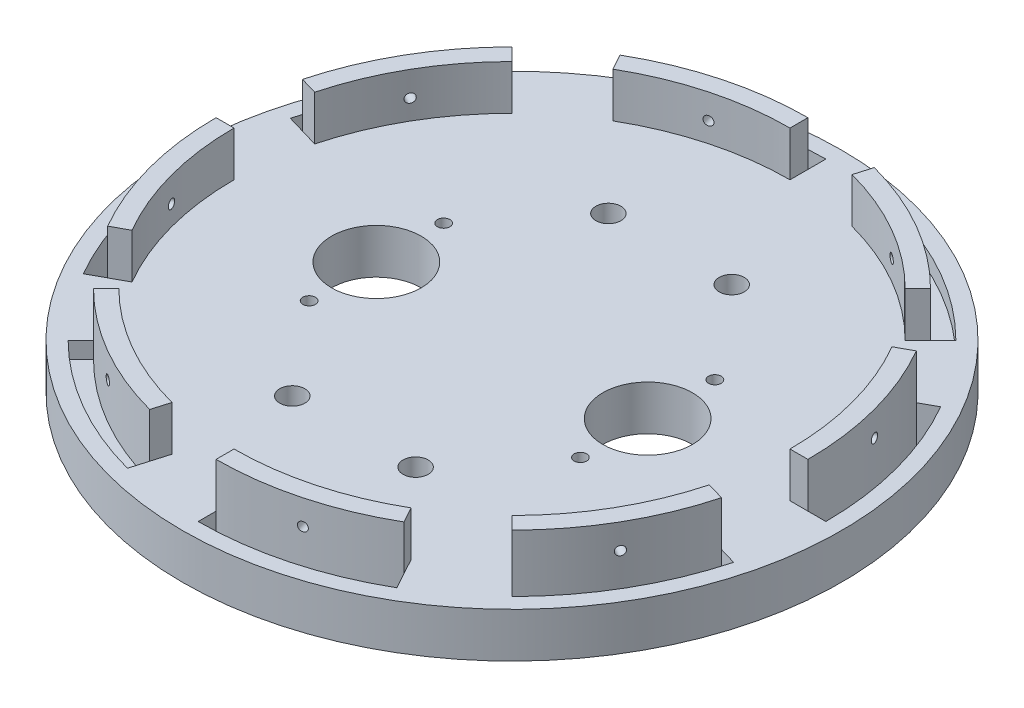
SolidWorks part; units mm, degrees
material "6061-T6 (SS)"
ref_plane "Front" through (0, 0, 0) normal (0, 0, 1) x (1, 0, 0)
ref_plane "Top" through (0, 0, 0) normal (0, 1, 0) x (1, 0, 0)
ref_plane "Right" through (0, 0, 0) normal (1, 0, 0) x (0, 0, -1)
sketch "Sketch1" plane through (0, 0, 0) normal (0, 1, 0) x (1, 0, 0)
  line L1 (0, 0) -> (127.635, 0)
  line L2 (0, 0) -> (0, 127.635)
  line L3 (0, 127.635) -> (127.635, 127.635)
  line L4 (127.635, 0) -> (127.635, 127.635)
  dimension "D1" = 127.635
  dimension "D2" = 127.635
extrude "Main Plate" add sketch "Sketch1" along normal blind 12.7
sketch "Sketch9" plane through (0, 12.7, 0) normal (0, 1, 0) x (1, 0, 0)
  circle A0 centre (63.8175, 63.8175) radius 93.345
  point P3 (0, 0)
  point P4 (0, 0)
  point P5 (0, 0)
  point P6 (0, 0)
  dimension "D1" = 186.69
  dimension "D2" = 63.8175
  dimension "D3" = 63.8175
extrude "Boss-Extrude1" add sketch "Sketch9" against normal up to surface (12.7 mm away) contours A0 up to face at (63.8175, 0, -63.8175)
sketch "Sketch11" plane through (0, 12.7, 0) normal (0, 1, 0) x (1, 0, 0)
  circle A0 centre (63.8175, 63.8175) radius 38.4175 construction
  circle A1 centre (63.8175, 63.8175) radius 42.8813 construction
  circle A2 centre (63.8175, 63.8175) radius 48.0528 construction
  point P3 (0, 0)
  point P5 (56.2292, 90.5407)
  point P8 (0, 0)
  dimension "D1" = 76.835
  dimension "D2" = 85.7626
  dimension "D3" = 96.1055
sketch "Sketch12" plane through (0, 12.7, 0) normal (0, 1, 0) x (1, 0, 0)
  line L0 (63.8175, 156.3529) -> (63.8175, -30.2474) construction
  line L1 (160.3603, 63.8175) -> (-31.9911, 63.8175) construction
sketch "Sketch2" plane through (0, 12.7, 0) normal (0, 1, 0) x (1, 0, 0)
  circle A0 centre (46.355, 108.585) radius 3.556
  circle A3 centre (63.8175, 63.8175) radius 48.0528 construction
  dimension "D1" = 7.112
extrude "U-Bolt Hole" cut sketch "Sketch2" against normal blind 12.7
pattern_linear "U-Bolt Pattern" count 2 spacing 34.925 along (1, 0, 0) count 2 spacing 89.535 along (0, 0, 1) of "U-Bolt Hole"
sketch "Sketch3" plane through (0, 12.7, 0) normal (0, 1, 0) x (1, 0, 0)
  circle A0 centre (25.4, 44.7675) radius 1.778
  circle A1 centre (63.8175, 63.8175) radius 42.8813 construction
  dimension "D1" = 3.556
extrude "Raptor Bolt Hole" cut sketch "Sketch3" against normal blind 12.7
pattern_linear "Raptor Bolt Pattern" count 2 spacing 38.1 along (0, 0, -1) count 2 spacing 76.835 along (1, 0, 0) of "Raptor Bolt Hole"
sketch "Sketch4" plane through (0, 12.7, 0) normal (0, 1, 0) x (1, 0, 0)
  circle A0 centre (25.4, 63.8175) radius 12.7
  circle A1 centre (63.8175, 63.8175) radius 38.4175 construction
  dimension "D1" = 25.4
extrude "Co2 Cylinder Hole" cut sketch "Sketch4" against normal blind 12.7
pattern_linear "Co2 Pattern" count 2 spacing 76.835 along (1, 0, 0) of "Co2 Cylinder Hole"
sketch "Sketch13" plane through (0, 12.7, 0) normal (0, 1, 0) x (1, 0, 0)
  line L0 (63.8175, 63.8175) -> (63.8175, 157.1625) construction
  line L1 (-50, 0) -> (50, 0) construction
  line L2 (63.8175, 147.6375) -> (63.8175, 152.7175)
  line L3 (19.4246, 140.8401) -> (21.8608, 136.3808)
  arc A0 (19.4246, 140.8401) -> (63.8175, 152.7175) centre (63.8175, 63.8175) cw
  arc A1 (21.8608, 136.3808) -> (63.8175, 147.6375) centre (63.8175, 63.8175) cw
  circle A2 centre (63.8175, 63.8175) radius 93.345 construction
  dimension "D1" = 83.82
  dimension "D2" = 88.9
  dimension "D3" = 43.942
  dimension "D4" = 46.482
extrude "Bottom support hole" cut sketch "Sketch13" against normal through all
sketch "Sketch14" plane through (0, 12.7, 0) normal (0, 1, 0) x (1, 0, 0)
  line L0 (63.8175, 147.6375) -> (63.8175, 142.5575)
  line L1 (24.297, 131.9213) -> (21.8608, 136.3808)
  line L4 (19.4246, 140.8401) -> (21.8608, 136.3808) construction
  arc A0 (63.8175, 142.5575) -> (24.297, 131.9213) centre (63.8175, 63.8175) ccw
  arc A1 (21.8608, 136.3808) -> (63.8175, 147.6375) centre (63.8175, 63.8175) cw
  point P6 (0, 0)
  point P9 (0, 0)
  dimension "D1" = 43.942
  dimension "D2" = 78.74
extrude "Bottom support guide" add sketch "Sketch14" along normal blind 12.7
ref_plane "Bottom bolt hole reference plane" through (-32.6653, 0, -121.7517) normal (0.2591, 0, 0.9658) x (0.9658, 0, -0.2591)
sketch "Sketch15" plane through (-32.6653, 0, -121.7517) normal (0.2591, 0, 0.9658) x (0.9658, 0, -0.2591)
  line L0 (99.8949, 25.4) -> (56.4544, 25.4) construction
  circle A0 centre (78.1779, 18.3381) radius 1.27
  dimension "D3" = 2.54
  dimension "D1" = 7.0619
  dimension "D2" = 21.717
extrude "Bottom bolt hole" cut sketch "Sketch15" against normal blind 12.7 and the other way blind 12.7
sketch "Sketch17" plane through (-29.8353, 12.7, 11.3946) normal (0, 1, 0) x (1, 0, 0)
  line L0 (93.6528, 75.2121) -> (27.6479, 141.217) construction
  line L2 (34.3831, 134.4818) -> (30.791, 138.0739)
  line L3 (7.7991, 98.2848) -> (12.675, 96.8542)
  line L4 (93.6528, 75.2121) -> (93.6528, 168.5571) construction
  arc A0 (7.7991, 98.2848) -> (30.791, 138.0739) centre (93.6528, 75.2121) cw
  arc A1 (12.675, 96.8542) -> (34.3831, 134.4818) centre (93.6528, 75.2121) cw
  circle A2 centre (93.6528, 75.2121) radius 93.345 construction
  point P3 (0, 0)
  point P6 (54.5809, 46.0878)
  point P8 (76.4675, 59.1533)
  point P9 (50.3325, 46.8384)
  point P13 (74.2776, 161.9751)
  point P14 (0, 0)
  point P15 (0, 0)
  point P18 (0, 0)
  dimension "D1" = 83.82
  dimension "D2" = 88.9
  dimension "D3" = 43.942
  dimension "D4" = 46.482
  dimension "D5" = 45
extrude "Top support hole" cut sketch "Sketch17" against normal blind 4.7625
sketch "Sketch19" plane through (-29.8353, 12.7, 11.3946) normal (0, 1, 0) x (1, 0, 0)
  line L0 (34.3831, 134.4818) -> (37.9752, 130.8897)
  line L1 (17.551, 95.4236) -> (12.675, 96.8542)
  line L2 (93.6528, 75.2121) -> (27.6479, 141.217) construction
  line L3 (7.7991, 98.2848) -> (12.675, 96.8542) construction
  arc A0 (37.9752, 130.8897) -> (17.551, 95.4236) centre (93.6528, 75.2121) ccw
  arc A1 (12.675, 96.8542) -> (34.3831, 134.4818) centre (93.6528, 75.2121) cw
  point P3 (0, 0)
  point P6 (0, 0)
  point P7 (0, 0)
  point P8 (-2.2794, 102.3671)
  point P9 (0, 0)
  point P10 (0, 0)
  point P11 (-2.9908, 105.4904)
  point P15 (0, 0)
  point P17 (0, 0)
  point P18 (45.2055, 119.1808)
  point P19 (13.2687, 98.9648)
  point P20 (0, 0)
  dimension "D1" = 43.942
  dimension "D2" = 78.74
extrude "Top support guide" add sketch "Sketch19" along normal blind 12.7
ref_plane "Plane2" through (-49.8664, 0, -28.769) normal (0.8662, 0, 0.4997) x (0.4997, 0, -0.8662)
sketch "Sketch21" plane through (-49.8664, 0, -28.769) normal (0.8662, 0, 0.4997) x (0.4997, 0, -0.8662)
  line L0 (108.8891, 25.4) -> (65.4485, 25.4) construction
  circle A0 centre (87.1721, 18.3381) radius 1.27
  dimension "D3" = 2.54
  dimension "D1" = 7.0619
  dimension "D2" = 21.717
extrude "Top bolt hole" cut sketch "Sketch21" against normal blind 12.7 and the other way blind 12.7
pattern_circular "Support pattern" count 4 over 360 about axis through (63.8175, 12.7, -63.8175) along (0, 1, 0) of "Bottom support hole", "Top bolt hole", "Top support guide", "Top support hole", "Bottom bolt hole", "Bottom support guide"
